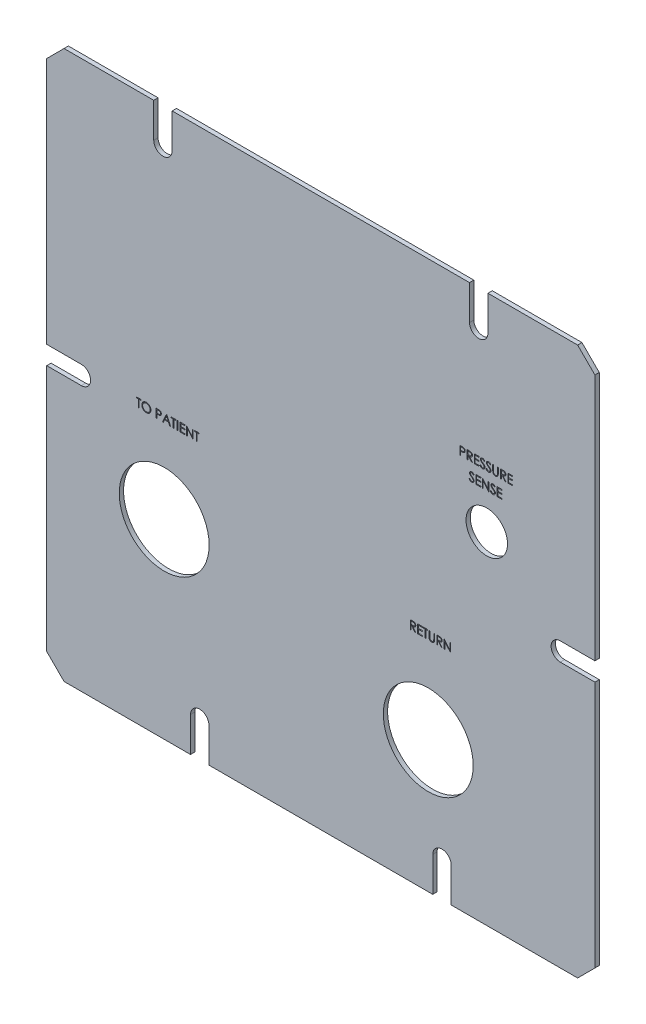
SolidWorks part; units mm, degrees
material "PE High Density"
ref_plane "Front" through (0, 0, 0) normal (0, 0, 1) x (1, 0, 0)
ref_plane "Top" through (0, 0, 0) normal (0, 1, 0) x (1, 0, 0)
ref_plane "Right" through (0, 0, 0) normal (1, 0, 0) x (0, 0, -1)
ref_axis "Axis1" through (0, 0, 55) along (0, 0, -1)
sketch "Sketch1" plane through (0, 0, 0) normal (0, 0, 1) x (1, 0, 0)
  line L1 (-100.584, 100.584) -> (100.584, 100.584)
  line L2 (-100.584, 100.584) -> (-100.584, -100.584)
  line L3 (-100.584, -100.584) -> (100.584, -100.584)
  line L4 (100.584, 100.584) -> (100.584, -100.584)
  line L5 (-100.584, 100.584) -> (100.584, -100.584) construction
  line L6 (-100.584, -100.584) -> (100.584, 100.584) construction
  point P0 (0, 0)
  dimension "D1" = 201.168
extrude "Boss-Extrude1" add sketch "Sketch1" along normal blind 1.5875
sketch "Sketch2" plane through (0, 0, 1.5875) normal (0, 0, 1) x (1, 0, 0)
  line L0 (100.584, -100.584) -> (100.584, 100.584) construction
  line L1 (100.584, 100.584) -> (-100.584, 100.584) construction
  circle A0 centre (-57.484, -30.636) radius 16.5
  circle A1 centre (39.4206, -52.284) radius 16.5
  dimension "D1" = 33
  dimension "D2" = 61.1634
  dimension "D3" = 158.068
  dimension "D4" = 131.22
  dimension "D5" = 152.868
extrude "Cut-Extrude1" cut sketch "Sketch2" against normal up to next
hole_wizard "1/4 Clearance Hole1" positions "Sketch3" profile "Sketch4" hole size "1/4" standard "ANSI Inch" end condition up to next
sketch "Sketch3" plane through (0, 0, 1.5875) normal (0, 0, 1) x (1, 0, 0)
  line L0 (0, 100.584) -> (0, -100.584) construction
  line L1 (100.584, 100.584) -> (-100.584, 100.584) construction
  line L2 (-100.584, -100.584) -> (100.584, -100.584) construction
  line L4 (-100.584, 0) -> (100.584, 0) construction
  line L5 (-100.584, 100.584) -> (-100.584, -100.584) construction
  line L6 (100.584, -100.584) -> (100.584, 100.584) construction
  line L8 (-57.9437, 87.884) -> (57.9438, 87.884) construction
  line L10 (-44.45, -87.884) -> (44.45, -87.884) construction
  point P0 (-57.9437, 87.884)
  point P2 (57.9438, 87.884)
  point P4 (87.884, 0)
  point P6 (-87.884, 0)
  point P8 (-44.45, -87.884)
  point P10 (44.45, -87.884)
  dimension "D1" = 12.7
  dimension "D2" = 115.8875
  dimension "D3" = 12.7
  dimension "D4" = 88.9
  dimension "D5" = 12.7
sketch "Sketch4" plane through (-57.9437, 87.884, 1.5875) normal (1, 0, 0) x (0, -1, 0)
  line L0 (0, 0) -> (0, 1.5875)
  line L1 (0, 1.5875) -> (3.3782, 1.5875)
  line L2 (3.3782, 1.5875) -> (3.3782, 0)
  line L5 (3.3782, 0) -> (0, 0)
  line L11 (0, -6.35) -> (0, 107.95) construction
  dimension "Thru Hole Dia." = 6.7564
  dimension "Thru Hole Depth" = 1.5875
chamfer "Chamfer1" distance 6.35 angle 45 4 edges at (-100.584, -100.584, 0.7937) (100.584, -100.584, 0.7937) (100.584, 100.584, 0.7937) (-100.584, 100.584, 0.7937)
sketch "Sketch5" plane through (0, 0, 1.5875) normal (0, 0, 1) x (1, 0, 0)
  line L0 (100.584, -20.534) -> (-100.584, -20.534) construction
  line L1 (100.584, -94.234) -> (100.584, 94.234) construction
  line L2 (-100.584, 94.234) -> (-100.584, -94.234) construction
  line L3 (-88.6311, 0) -> (87.884, 0) construction
  line L4 (-57.484, -30.636) -> (-57.484, 100.584) construction
  line L5 (94.234, 100.584) -> (-94.234, 100.584) construction
  line L6 (39.4206, -52.284) -> (39.4206, 100.584) construction
  circle A0 centre (39.4206, -52.284) radius 16.5 construction
  text T0 "TO PATIENT"
  text T1 "RETURN                                           "
  dimension "D1" = 39.4206
  dimension "D2" = 107.1483
  dimension "D3" = 31.75
extrude "Cut-Extrude2" cut sketch "Sketch5" against normal blind 0.508
sketch "Sketch6" plane through (0, 0, 1.5875) normal (0, 0, 1) x (1, 0, 0)
  line L0 (-61.3219, 87.884) -> (-54.5655, 87.884) construction
  line L1 (54.5656, 87.884) -> (61.322, 87.884) construction
  line L2 (-47.8282, -87.884) -> (-41.0718, -87.884) construction
  line L3 (-61.3219, 87.884) -> (-54.5655, 87.884)
  line L4 (-61.3219, 87.884) -> (-61.3219, 102.362)
  line L5 (-61.3219, 102.362) -> (-54.5655, 102.362)
  line L6 (-54.5655, 87.884) -> (-54.5655, 102.362)
  line L7 (-61.3219, 87.884) -> (-54.5655, 102.362) construction
  line L8 (-61.3219, 102.362) -> (-54.5655, 87.884) construction
  line L9 (54.5656, 87.884) -> (61.322, 87.884)
  line L10 (54.5656, 87.884) -> (54.5656, 102.362)
  line L11 (54.5656, 102.362) -> (61.322, 102.362)
  line L12 (61.322, 87.884) -> (61.322, 102.362)
  line L13 (54.5656, 87.884) -> (61.322, 102.362) construction
  line L14 (54.5656, 102.362) -> (61.322, 87.884) construction
  line L15 (41.0718, -87.884) -> (47.8282, -87.884) construction
  line L16 (-87.884, 3.3782) -> (-87.884, -3.3782) construction
  line L17 (-47.8282, -87.884) -> (-41.0718, -87.884)
  line L18 (-47.8282, -87.884) -> (-47.8282, -102.362)
  line L19 (-47.8282, -102.362) -> (-41.0718, -102.362)
  line L20 (-41.0718, -87.884) -> (-41.0718, -102.362)
  line L21 (-47.8282, -87.884) -> (-41.0718, -102.362) construction
  line L22 (-47.8282, -102.362) -> (-41.0718, -87.884) construction
  line L23 (41.0718, -87.884) -> (47.8282, -87.884)
  line L24 (41.0718, -87.884) -> (41.0718, -102.362)
  line L25 (41.0718, -102.362) -> (47.8282, -102.362)
  line L26 (47.8282, -87.884) -> (47.8282, -102.362)
  line L27 (41.0718, -87.884) -> (47.8282, -102.362) construction
  line L28 (41.0718, -102.362) -> (47.8282, -87.884) construction
  line L29 (87.884, 3.3782) -> (87.884, -3.3782) construction
  line L31 (-87.884, -3.3782) -> (-102.362, -3.3782)
  line L32 (-87.884, -3.3782) -> (-87.884, 3.3782)
  line L33 (-87.884, 3.3782) -> (-102.362, 3.3782)
  line L34 (-102.362, -3.3782) -> (-102.362, 3.3782)
  line L35 (-87.884, -3.3782) -> (-102.362, 3.3782) construction
  line L36 (-87.884, 3.3782) -> (-102.362, -3.3782) construction
  line L37 (87.884, -3.3782) -> (102.362, -3.3782)
  line L38 (87.884, -3.3782) -> (87.884, 3.3782)
  line L39 (87.884, 3.3782) -> (102.362, 3.3782)
  line L40 (102.362, -3.3782) -> (102.362, 3.3782)
  line L41 (87.884, -3.3782) -> (102.362, 3.3782) construction
  line L42 (87.884, 3.3782) -> (102.362, -3.3782) construction
  circle A0 centre (-57.9437, 87.884) radius 3.3782 construction
  circle A1 centre (57.9438, 87.884) radius 3.3782 construction
  circle A2 centre (-44.45, -87.884) radius 3.3782 construction
  circle A3 centre (44.45, -87.884) radius 3.3782 construction
  circle A4 centre (-87.884, 0) radius 3.3782 construction
  circle A5 centre (87.884, 0) radius 3.3782 construction
  point P13 (-57.9437, 95.123)
  point P17 (57.9438, 95.123)
  point P29 (-44.45, -95.123)
  point P33 (44.45, -95.123)
  point P45 (-95.123, 0)
  point P49 (95.123, 0)
  dimension "D1" = 14.478
extrude "Cut-Extrude3" cut sketch "Sketch6" against normal up to next
sketch "Sketch7" plane through (0, 0, 1.5875) normal (0, 0, 1) x (1, 0, 0)
  circle A0 centre (60.8965, 24.511) radius 7.62
  dimension "D1" = 15.24
extrude "Cut-Extrude4" cut sketch "Sketch7" against normal up to next
sketch "Sketch8" plane through (0, 0, 1.5875) normal (0, 0, 1) x (1, 0, 0)
  line L0 (100.584, 3.3782) -> (100.584, 94.234) construction
  line L1 (94.234, 100.584) -> (61.322, 100.584) construction
  text T0 "PRESSURE\r\n   SENSE"
  dimension "D1" = 49.956
  dimension "D2" = 56.6691
extrude "Cut-Extrude5" cut sketch "Sketch8" against normal blind 0.508
